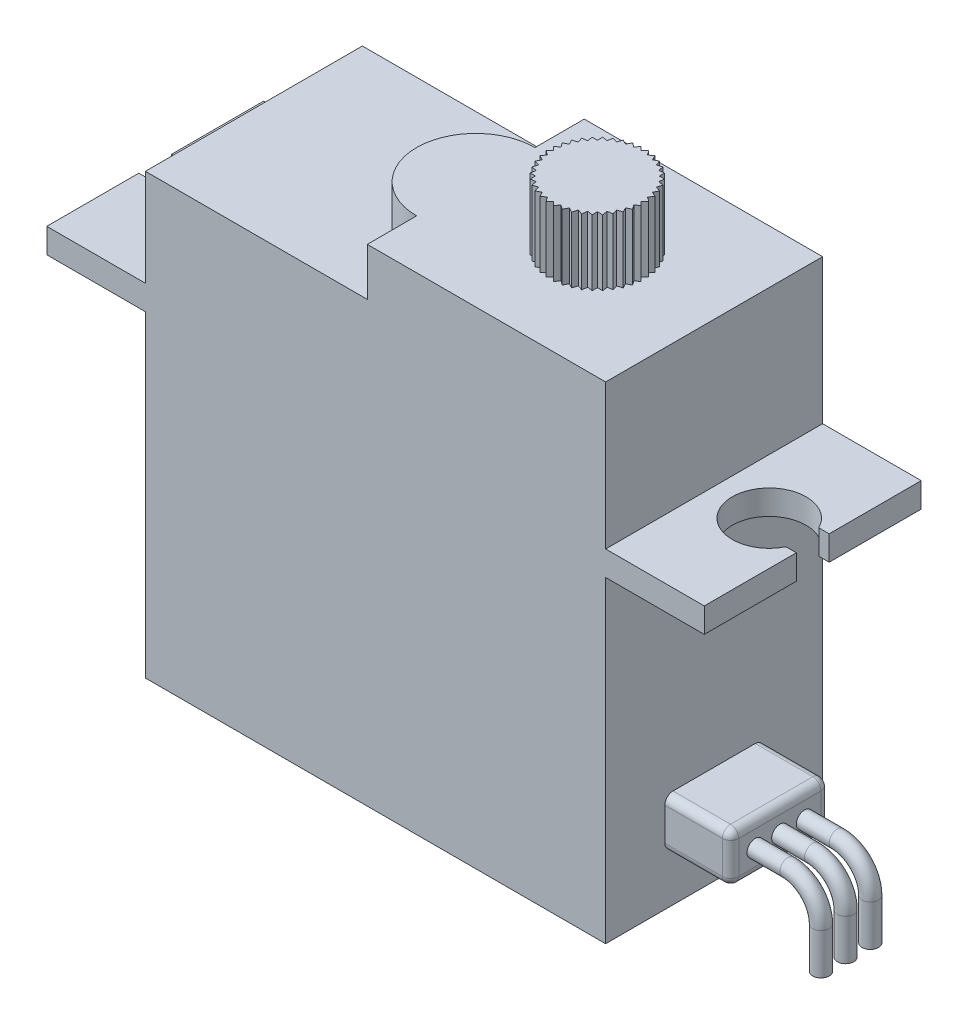
SolidWorks part; units mm, degrees
ref_plane "Płaszczyzna przednia" through (0, 0, 0) normal (0, 0, 1) x (1, 0, 0)
ref_plane "Płaszczyzna górna" through (0, 0, 0) normal (0, 1, 0) x (1, 0, 0)
ref_plane "Płaszczyzna prawa" through (0, 0, 0) normal (1, 0, 0) x (0, 0, -1)
sketch "Szkic1" plane through (0, 0, 0) normal (0, 1, 0) x (1, 0, 0)
  line L0 (-24.25, 0) -> (10.45, 0) construction
  line L1 (-20.9, -6.6) -> (7.1, -6.6)
  line L2 (-20.9, -6.6) -> (-20.9, 6.6)
  line L3 (-20.9, 6.6) -> (7.1, 6.6)
  line L4 (7.1, -6.6) -> (7.1, 6.6)
  line L5 (-20.9, -6.6) -> (7.1, 6.6) construction
  line L6 (-20.9, 6.6) -> (7.1, -6.6) construction
  line L7 (-26.9, -6.6) -> (13.1, -6.6)
  line L8 (-26.9, -6.6) -> (-26.9, -1)
  line L9 (-26.9, 6.6) -> (13.1, 6.6)
  line L10 (13.1, -6.6) -> (13.1, -1)
  line L11 (-26.9, -6.6) -> (13.1, 6.6) construction
  line L12 (-26.9, 6.6) -> (13.1, -6.6) construction
  line L13 (-7.4, 3.6) -> (-7.4, 6.6)
  line L14 (-7.4, -3.6) -> (-7.4, -6.6)
  line L15 (-26.2656, -1) -> (-26.9, -1)
  line L16 (-26.2656, 1) -> (-26.9, 1)
  line L17 (12.4656, 1) -> (13.1, 1)
  line L18 (12.4656, -1) -> (13.1, -1)
  line L19 (-26.9, 1) -> (-26.9, 6.6)
  line L20 (13.1, 1) -> (13.1, 6.6)
  line L21 (-7.4, 6.6) -> (7.1, 6.6)
  line L22 (7.1, -6.6) -> (-7.4, -6.6)
  line L23 (7.1, -6.6) -> (7.1, 6.6)
  arc A1 (-26.2656, -1) -> (-26.2656, 1) centre (-24.25, 0) ccw
  arc A2 (12.4656, 1) -> (12.4656, -1) centre (10.45, 0) ccw
  arc A3 (-7.4, -3.6) -> (-7.4, 3.6) centre (-7.4, 0) cw
  circle A4 centre (0, 0) radius 2.9
  point P15 (-6.9, 0)
  point P16 (-6.9, 0)
  point P28 (-7.4, 5.5588)
  point P29 (0, 0)
  dimension "D3" = 40
  dimension "D5" = 4.5
  dimension "D6" = 18.1
  dimension "D4" = 34.7
  dimension "D9" = 5.8
  dimension "D10" = 4.2
  dimension "D1" = 13.2
  dimension "D2" = 28
  dimension "D7" = 14.5
  dimension "D8" = 2
extrude "Dodanie-wyciągnięcie1" add sketch "Szkic1" along normal blind 26.7 contours L14 A3 L13 L3 L2 L1 | A3 L14 L7 L4 L9 L13 A4 | A4 | A4 | L2 L1 L4 L3 region at (-14.8235, 0, 0) region at (-7.176, 0, 5.1) region at (0, 0, 0)
extrude "Dodanie-wyciągnięcie2" add sketch "Szkic1<3>" along normal blind 1.5 from offset 19.3 contours A2 L17 L20 L9 L4 L7 L10 L18 | A1 L15 L8 L7 L2 L9 L19 L16 region at (-23.9, 0, 6.455) region at (7.245, 0, 0)
sketch "Szkic1<3>" plane through (0, 0, 0) normal (0, 1, 0) x (1, 0, 0) same geometry as "Szkic1"
extrude "Dodanie-wyciągnięcie3" add sketch "Szkic1<4>" along normal blind 29.6 contours A3 L14 L7 L4 L9 L13 | A4 region at (-7.176, 0, 5.1)
sketch "Szkic1<4>" plane through (0, 0, 0) normal (0, 1, 0) x (1, 0, 0) same geometry as "Szkic1"
extrude "Dodanie-wyciągnięcie4" add sketch "Szkic1<5>" along normal blind 4 from surface contours A4 region at (0, 0, 0) starting at face at (-3.1667, 29.6, 0)
sketch "Szkic1<5>" plane through (0, 0, 0) normal (0, 1, 0) x (1, 0, 0) same geometry as "Szkic1"
ref_axis "Oś1" through (0, 47.1716, 0) along (0, -1, 0)
sketch "Szkic3" plane through (0, 33.6, 0) normal (0, 1, 0) x (1, 0, 0)
  line L0 (-0.2275, 2.8911) -> (0, 2.6635)
  line L1 (0, 2.6635) -> (0.2275, 2.8911)
  line L2 (0.2275, 2.8911) -> (0.2275, 3.6635)
  line L3 (0.2275, 3.6635) -> (-0.2275, 3.6635)
  line L4 (-0.2275, 3.6635) -> (-0.2275, 2.8911)
  line L5 (-0.2275, 2.8911) -> (0, 0) construction
  line L6 (0, 0) -> (0.2275, 2.8911) construction
  circle A0 centre (0, 0) radius 2.9 construction
  point P4 (0, 0)
  point P10 (0.2531, 2.893)
  dimension "D1" = 9
  dimension "D2" = 1
extrude "Wytnij-wyciągnięcie1" cut sketch "Szkic3" against normal up to surface (4 mm away) up to face at (0, 29.6, 2.9)
pattern_circular "Szyk kołowy1" count 40 over 360 about axis through (0, 33.6, 0) along (0, -1, 0) of "Wytnij-wyciągnięcie1" reverse direction yes
sketch "Szkic4" plane through (7.1, 0, 0) normal (1, 0, 0) x (0, 0, -1)
  line L0 (-6.6, 0) -> (6.6, 0) construction
  line L1 (-2.5, 3) -> (2.5, 3)
  line L2 (-3, 3.5) -> (-3, 5.5)
  line L3 (-2.5, 6) -> (2.5, 6)
  line L4 (3, 3.5) -> (3, 5.5)
  line L5 (-3, 3) -> (3, 6) construction
  line L6 (-3, 6) -> (3, 3) construction
  arc A0 (2.5, 6) -> (3, 5.5) centre (2.5, 5.5) cw
  arc A1 (2.5, 3) -> (3, 3.5) centre (2.5, 3.5) ccw
  arc A2 (-2.5, 3) -> (-3, 3.5) centre (-2.5, 3.5) cw
  arc A3 (-3, 5.5) -> (-2.5, 6) centre (-2.5, 5.5) cw
  point P0 (0, 4.5)
  point P7 (-2.025, 6)
  point P8 (0, 0)
  dimension "D4" = 0.5
  dimension "D1" = 3
  dimension "D2" = 6
  dimension "D3" = 3
extrude "Dodanie-wyciągnięcie5" add sketch "Szkic4" along normal blind 4
fillet "Zaokrąglenie1" radius 0.5 8 edges at (11.1, 5.8536, -2.8536) (11.1, 4.5, -3) (11.1, 3.1464, -2.8536) (11.1, 3, 0) (11.1, 3.1464, 2.8536) (11.1, 4.5, 3) (11.1, 5.8536, 2.8536) (11.1, 6, 0)
sketch "Szkic5" plane through (11.1, 0, 0) normal (1, 0, 0) x (0, 0, -1)
  line L0 (-1.5, 4.5) -> (0, 4.5) construction
  line L1 (0, 4.5) -> (1.5, 4.5) construction
  line L8 (-2.5, 3.5) -> (2.5, 3.5)
  line L9 (2.5, 3.5) -> (2.5, 5.5)
  line L10 (2.5, 5.5) -> (-2.5, 5.5)
  line L11 (-2.5, 5.5) -> (-2.5, 3.5)
  line L12 (-2.5, 3.5) -> (2.5, 3.5) construction
  line L13 (2.5, 3.5) -> (2.5, 5.5) construction
  line L14 (2.5, 5.5) -> (-2.5, 5.5) construction
  line L15 (-2.5, 5.5) -> (-2.5, 3.5) construction
  circle A0 centre (-1.5, 4.5) radius 0.5
  circle A1 centre (0, 4.5) radius 0.5
  circle A2 centre (1.5, 4.5) radius 0.5
  point P6 (-2.5, 4.5)
  point P7 (0, 5.5)
  point P8 (1.6051, 4.5)
  point P11 (1.4643, 4.5)
  dimension "D1" = 0
  dimension "D2" = 1
  dimension "D3" = 1.5
sketch "Szkic6" plane through (0, 0, 0) normal (0, 0, 1) x (1, 0, 0)
  line L0 (11.1, 4.5) -> (13.1, 4.5)
  line L1 (15.1, 2.5) -> (15.1, 0)
  arc A0 (13.1, 4.5) -> (15.1, 2.5) centre (13.1, 2.5) cw
  point P5 (0, 0)
  point P7 (17.3253, 2.5)
  dimension "D1" = 2
  dimension "D2" = 2
sweep "Wyciągnięcie po ścieżce1" add profiles "Szkic5" path "Szkic6"
